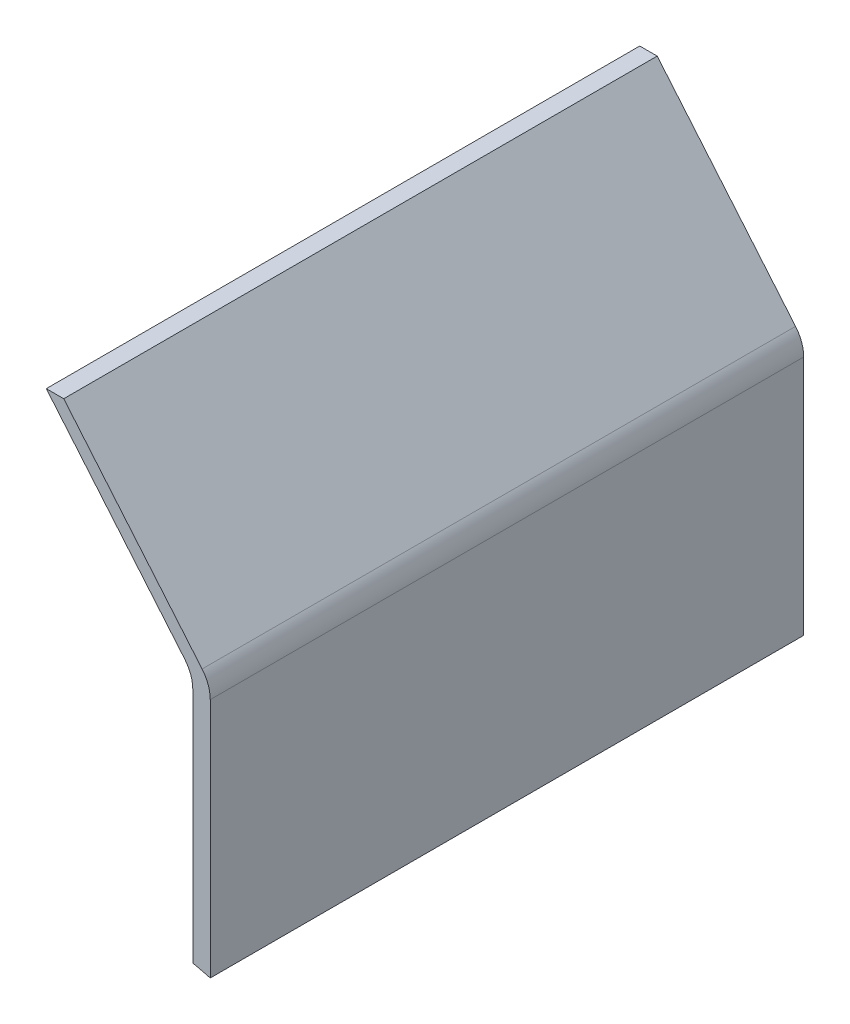
SolidWorks part; units mm, degrees
material "201 Annealed Stainless Steel (SS)"
ref_plane "Front Plane" through (0, 0, 0) normal (0, 0, 1) x (1, 0, 0)
ref_plane "Top Plane" through (0, 0, 0) normal (0, 1, 0) x (1, 0, 0)
ref_plane "Right Plane" through (0, 0, 0) normal (1, 0, 0) x (0, 0, -1)
sketch "Sketch1" plane through (0, 0, 0) normal (0, 0, 1) x (1, 0, 0)
  line L1 (-5, 1.2022) -> (-5, 72.7)
  line L2 (-5, 72.7) -> (-46.974, 122.7227)
  line L3 (-46.974, 122.7227) -> (-41.974, 122.7227)
  line L4 (-41.974, 122.7227) -> (0, 72.7)
  line L5 (0, 72.7) -> (0, 0)
  line L6 (-39.9, -154.9451) -> (-39.9, 5.0549) construction
  line L7 (-39.9, -154.9451) -> (0, -154.9451) construction
  line L8 (0, -154.9451) -> (0, 0) construction
  arc A0 (0, 0) -> (-5, 1.2022) centre (-39.9, -154.9451) ccw
  point P9 (0, -26.1759)
  point P13 (0, 0)
  dimension "D6" = 320
  dimension "D3" = 5
  dimension "D1" = 71.4978
  dimension "D2" = 5
  dimension "D4" = 140
  dimension "D5" = 65.3
  dimension "D7" = 39.9
extrude "Funnel - Left Side" add sketch "Sketch1" along normal blind 170
fillet "Fillet1" radius 10 2 edges at (0, 72.7, 85) (-5, 72.7, 85)
